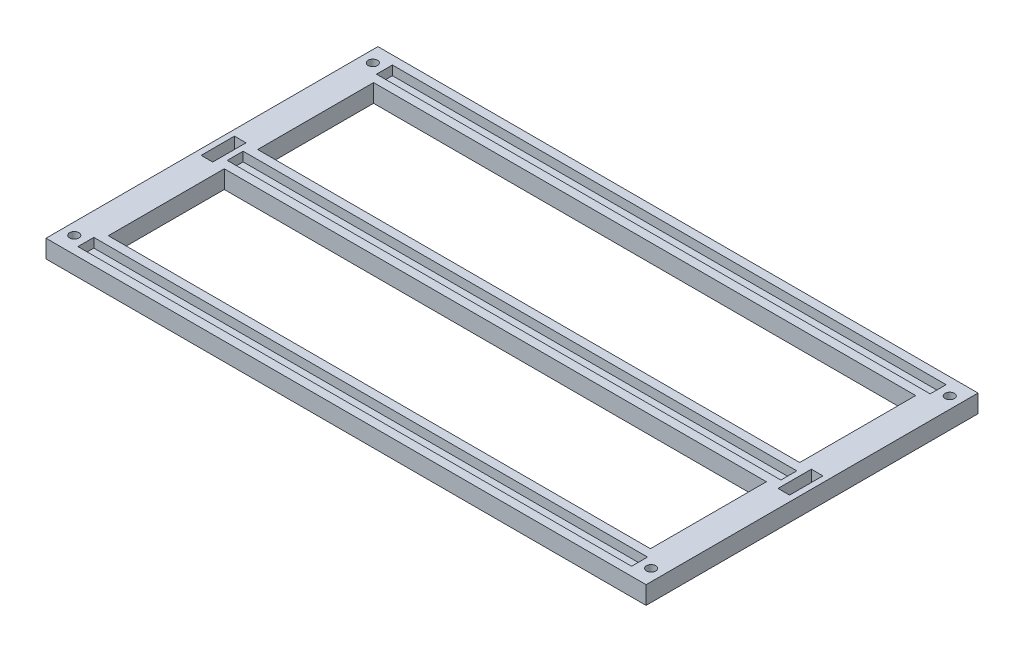
SolidWorks part; units mm, degrees
ref_plane "Front Plane" through (0, 0, 0) normal (0, 0, 1) x (1, 0, 0)
ref_plane "Top Plane" through (0, 0, 0) normal (0, 1, 0) x (1, 0, 0)
ref_plane "Right Plane" through (0, 0, 0) normal (1, 0, 0) x (0, 0, -1)
sketch "Sketch1" plane through (0, 0, 0) normal (0, 1, 0) x (1, 0, 0)
  line L0 (-93.5, 45.75) -> (-93.5, 48.75)
  line L1 (-103.5, -57.25) -> (103.5, -57.25)
  line L2 (-103.5, -57.25) -> (-103.5, 57.25)
  line L3 (-103.5, 57.25) -> (103.5, 57.25)
  line L4 (103.5, -57.25) -> (103.5, 57.25)
  line L5 (0, 57.25) -> (0, -57.25) construction
  line L6 (-103.5, 0) -> (103.5, 0) construction
  line L7 (-93.5, 45.75) -> (93.5, 45.75)
  line L8 (-93.5, 45.75) -> (-93.5, 5.75)
  line L9 (-93.5, 5.75) -> (93.5, 5.75)
  line L10 (93.5, 45.75) -> (93.5, 5.75)
  line L11 (-93.5, -5.75) -> (93.5, -5.75)
  line L12 (-93.5, -5.75) -> (-93.5, -45.75)
  line L13 (-93.5, -45.75) -> (93.5, -45.75)
  line L14 (93.5, -5.75) -> (93.5, -45.75)
  line L15 (-93.5, 48.75) -> (-95.5, 48.75)
  line L16 (-95.5, 48.75) -> (-95.5, 54.25)
  line L17 (-95.5, 54.25) -> (-93.5, 54.25)
  line L18 (-93.5, 54.25) -> (-93.5, 57.25)
  line L19 (93.5, 45.75) -> (93.5, 48.75)
  line L20 (93.5, 48.75) -> (95.5, 48.75)
  line L21 (95.5, 48.75) -> (95.5, 54.25)
  line L22 (95.5, 54.25) -> (93.5, 54.25)
  line L23 (93.5, 54.25) -> (93.5, 57.25)
  line L24 (93.5, 2.75) -> (93.5, 5.75)
  line L25 (95.5, 2.75) -> (93.5, 2.75)
  line L26 (95.5, -2.75) -> (95.5, 2.75)
  line L27 (93.5, -2.75) -> (95.5, -2.75)
  line L28 (93.5, -5.75) -> (93.5, -2.75)
  line L29 (-93.5, 2.75) -> (-93.5, 5.75)
  line L30 (-95.5, 2.75) -> (-93.5, 2.75)
  line L31 (-95.5, -2.75) -> (-95.5, 2.75)
  line L32 (-93.5, -2.75) -> (-95.5, -2.75)
  line L33 (-93.5, -5.75) -> (-93.5, -2.75)
  line L34 (93.5, -48.75) -> (93.5, -45.75)
  line L35 (95.5, -48.75) -> (93.5, -48.75)
  line L36 (95.5, -54.25) -> (95.5, -48.75)
  line L37 (93.5, -54.25) -> (95.5, -54.25)
  line L38 (93.5, -57.25) -> (93.5, -54.25)
  line L39 (-93.5, -48.75) -> (-93.5, -45.75)
  line L40 (-95.5, -48.75) -> (-93.5, -48.75)
  line L41 (-95.5, -54.25) -> (-95.5, -48.75)
  line L42 (-93.5, -54.25) -> (-95.5, -54.25)
  line L43 (-93.5, -57.25) -> (-93.5, -54.25)
  line L44 (-93.5, 54.25) -> (93.5, 54.25)
  line L45 (-93.5, 48.75) -> (93.5, 48.75)
  line L46 (-93.5, 5.75) -> (-103.5, 5.75) construction
  line L47 (93.5, -48.75) -> (-93.5, -48.75)
  line L48 (-93.5, -54.25) -> (93.5, -54.25)
  line L49 (-93.5, 2.75) -> (93.5, 2.75)
  line L50 (95.5, 54.25) -> (103.5, 54.25) construction
  line L51 (95.5, 48.75) -> (103.5, 48.75) construction
  line L52 (99.5, 54.25) -> (99.5, 48.75) construction
  line L53 (0, -55) -> (0, 55) construction
  line L54 (-93.5, -5.75) -> (-103.5, -5.75) construction
  line L55 (93.5, 5.75) -> (103.5, 5.75) construction
  line L56 (93.5, -5.75) -> (103.5, -5.75) construction
  line L57 (-93.5, -2.75) -> (93.5, -2.75)
  line L58 (97.5, 5.75) -> (101.5, 5.75)
  line L59 (-97.5, -5.75) -> (-101.5, -5.75)
  line L60 (-97.5, -5.75) -> (-97.5, 5.75)
  line L61 (-97.5, 5.75) -> (-101.5, 5.75)
  line L62 (-101.5, -5.75) -> (-101.5, 5.75)
  line L63 (-99.5, 5.75) -> (-99.5, -5.75) construction
  line L64 (-97.5, 0) -> (-101.5, 0) construction
  line L65 (101.5, -5.75) -> (101.5, 5.75)
  line L66 (97.5, -5.75) -> (101.5, -5.75)
  line L67 (97.5, -5.75) -> (97.5, 5.75)
  circle A0 centre (99.5, 51.5) radius 1.6
  circle A1 centre (-99.5, 51.5) radius 1.6
  circle A2 centre (-99.5, 0) radius 1.6 construction
  circle A3 centre (99.5, 0) radius 1.6 construction
  circle A4 centre (-99.5, -51.5) radius 1.6
  circle A5 centre (99.5, -51.5) radius 1.6
  point P0 (0, 0)
  point P49 (-99.5, -5.75)
  dimension "D13" = 3.2
  dimension "D1" = 114.5
  dimension "D2" = 207
  dimension "D3" = 5.5
  dimension "D4" = 11.5
  dimension "D5" = 2
  dimension "D6" = 11.5
  dimension "D7" = 3
  dimension "D8" = 10
  dimension "D9" = 10
  dimension "D10" = 2
  dimension "D12" = 3
  dimension "D14" = 3
extrude "Boss-Extrude1" add sketch "Sketch1" along normal blind 3.2 contours L18 L44 L23 L3 | L45 L0 L7 L19 | L1 L43 L42 L41 L40 L39 L12 L33 L32 L31 L30 L29 L8 L0 L15 L16 L17 L18 L3 L2 A2 A1 A4 | L29 L24 L9 | L33 L11 L28 | L39 L34 L13 | L43 L1 L38 | L38 L1 L4 L3 L23 L22 L21 L20 L19 L10 L24 L25 L26 L27 L28 L14 L34 L35 L36 L37 A5 A3 A0 region at (-94.6494, 0, -25.75) region at (0, 0, -47.25) region at (94.6494, 0, -47.25) region at (0, 0, -4.25) region at (0, 0, -55.75) region at (0, 0, 4.25) region at (0, 0, 47.25) region at (0, 0, 55.75)
extrude "Boss-Extrude2" add sketch "Sketch1<3>" against normal blind 3 contours L38 L1 L4 L3 L23 L22 L21 L20 L19 L10 L24 L25 L26 L27 L28 L14 L34 L35 L36 L37 A5 A3 A0 | L42 L37 L36 L35 L40 L41 | L43 L1 L38 | L39 L34 L13 | L33 L11 L28 | L32 L27 L26 L25 L30 L31 | L29 L24 L9 | L45 L0 L7 L19 | L15 L45 L20 L21 L22 L44 L17 L16 | L18 L44 L23 L3 | L1 L43 L42 L41 L40 L39 L12 L33 L32 L31 L30 L29 L8 L0 L15 L16 L17 L18 L3 L2 A2 A1 A4 region at (-94.6494, 0, -25.75) region at (0, 0, -47.25) region at (0, 0, -51.5) region at (94.6494, 0, -47.25) region at (0, 0, -4.25) region at (0, 0, 0) region at (0, 0, -55.75) region at (0, 0, 4.25) region at (0, 0, 47.25) region at (0, 0, 55.75) region at (0, 0, 51.5)
sketch "Sketch1<3>" plane through (0, 0, 0) normal (0, 1, 0) x (1, 0, 0) same geometry as "Sketch1"
